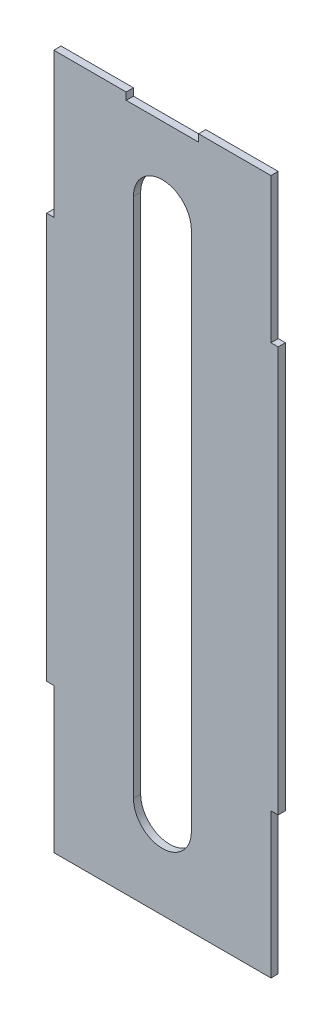
SolidWorks part; units mm, degrees
ref_plane "Front Plane" through (0, 0, 0) normal (0, 0, 1) x (1, 0, 0)
ref_plane "Top Plane" through (0, 0, 0) normal (0, 1, 0) x (1, 0, 0)
ref_plane "Right Plane" through (0, 0, 0) normal (1, 0, 0) x (0, 0, -1)
sketch "Sketch2" plane through (0, 0, 0) normal (0, 0, 1) x (1, 0, 0)
  line L1 (-803.1768, 65.3086) -> (-1019.0768, 65.3086)
  line L2 (-803.1768, 65.3086) -> (-803.1768, 674.9086)
  line L3 (-803.1768, 674.9086) -> (-1019.0768, 674.9086)
  line L4 (-1019.0768, 65.3086) -> (-1019.0768, 674.9086)
  line L5 (-803.1768, 65.3086) -> (-1019.0768, 674.9086) construction
  line L6 (-803.1768, 674.9086) -> (-1019.0768, 65.3086) construction
  dimension "D1" = 215.9
  dimension "D2" = 609.6
extrude "Boss-Extrude1" add sketch "Sketch2" along normal blind 6.35
sketch "Sketch3" plane through (0, 0, 6.35) normal (0, 0, 1) x (1, 0, 0)
  line L0 (-911.1268, 674.9086) -> (-911.1268, 65.3086) construction
  line L1 (-803.1768, 674.9086) -> (-1019.0768, 674.9086) construction
  line L2 (-1019.0768, 65.3086) -> (-803.1768, 65.3086) construction
  line L3 (-803.1768, 370.1086) -> (-1019.0768, 370.1086) construction
  line L4 (-803.1768, 65.3086) -> (-803.1768, 674.9086) construction
  line L5 (-1019.0768, 674.9086) -> (-1019.0768, 65.3086) construction
  line L6 (-911.1268, 141.5086) -> (-911.1268, 598.7086) construction
  line L7 (-936.5268, 141.5086) -> (-936.5268, 598.7086)
  line L8 (-885.7268, 141.5086) -> (-885.7268, 598.7086)
  arc A0 (-936.5268, 141.5086) -> (-885.7268, 141.5086) centre (-911.1268, 141.5086) ccw
  arc A1 (-885.7268, 598.7086) -> (-936.5268, 598.7086) centre (-911.1268, 598.7086) ccw
  point P14 (-911.1268, 370.1086)
extrude "Cut-Extrude1" cut sketch "Sketch3" against normal through all contours L8 A1 L7 A0
sketch "Sketch4" plane through (0, 0, 6.35) normal (0, 0, 1) x (1, 0, 0)
  line L0 (-815.8768, 674.9086) -> (-815.8768, 547.9086)
  line L1 (-803.1768, 674.9086) -> (-1019.0768, 674.9086) construction
  line L2 (-815.8768, 547.9086) -> (-803.1768, 547.9086)
  line L3 (-803.1768, 65.3086) -> (-803.1768, 674.9086) construction
extrude "Cut-Extrude2" cut sketch "Sketch4" against normal through all and the other way through all
sketch "Sketch5" plane through (0, 0, 6.35) normal (0, 0, 1) x (1, 0, 0)
  line L0 (-815.8768, 65.3086) -> (-815.8768, 192.3086)
  line L1 (-1019.0768, 65.3086) -> (-803.1768, 65.3086) construction
  line L2 (-815.8768, 192.3086) -> (-803.1768, 192.3086)
  line L3 (-803.1768, 65.3086) -> (-803.1768, 547.9086) construction
extrude "Cut-Extrude3" cut sketch "Sketch5" against normal through all and the other way through all flip side to cut
sketch "Sketch6" plane through (0, 0, 6.35) normal (0, 0, 1) x (1, 0, 0)
  line L0 (-1006.3768, 674.9086) -> (-1006.3768, 547.9086)
  line L1 (-815.8768, 674.9086) -> (-1019.0768, 674.9086) construction
  line L2 (-1006.3768, 547.9086) -> (-1019.0768, 547.9086)
  line L3 (-1019.0768, 674.9086) -> (-1019.0768, 65.3086) construction
extrude "Cut-Extrude6" cut sketch "Sketch6" against normal through all and the other way through all flip side to cut
ref_plane "Plane1" through (-1006.3768, 674.9086, 6.35) normal (-1, 0, 0) x (0, 0, 1)
sketch "Sketch9" plane through (0, 0, 6.35) normal (0, 0, 1) x (1, 0, 0)
  line L0 (-1006.3768, 65.3086) -> (-1006.3768, 192.3086)
  line L1 (-1019.0768, 65.3086) -> (-815.8768, 65.3086) construction
  line L2 (-1006.3768, 192.3086) -> (-1019.0768, 192.3086)
  line L3 (-1019.0768, 547.9086) -> (-1019.0768, 65.3086) construction
extrude "Cut-Extrude7" cut sketch "Sketch9" against normal through all and the other way through all
ref_plane "Plane2" through (-1006.3768, 65.3086, 6.35) normal (1, 0, 0) x (0, 0, -1)
sketch "Sketch13" plane through (0, 0, 0) normal (0, 0, -1) x (-1, 0, 0)
  line L2 (815.8768, 674.9086) -> (1006.3768, 674.9086) construction
  line L5 (879.3768, 668.5586) -> (879.3768, 674.9086)
  line L6 (942.8768, 668.5586) -> (942.8768, 674.9086)
  line L7 (942.8768, 668.5586) -> (879.3768, 668.5586)
ref_plane "Plane3" through (-803.1768, 192.3086, 0) normal (-1, 0, 0) x (0, 0, 1)
ref_plane "Plane10" through (-1019.0768, 192.3086, 6.35) normal (1, 0, 0) x (0, 0, -1)
sketch "Sketch16" plane through (0, 0, 6.35) normal (0, 0, 1) x (1, 0, 0)
  line L2 (-1012.7268, 192.3086) -> (-1012.7268, 547.9086)
  line L3 (-1019.0768, 192.3086) -> (-1006.3768, 192.3086) construction
  line L4 (-1019.0768, 547.9086) -> (-1006.3768, 547.9086) construction
extrude "Cut-Extrude11" cut sketch "Sketch16" against normal through all and the other way through all
sketch "Sketch17" plane through (0, 0, 6.35) normal (0, 0, 1) x (1, 0, 0)
  line L2 (-809.5268, 192.3086) -> (-809.5268, 547.9086)
  line L3 (-803.1768, 547.9086) -> (-815.8768, 547.9086) construction
extrude "Cut-Extrude13" cut sketch "Sketch17" against normal through all and the other way through all flip side to cut
extrude "Cut-Extrude14" cut sketch "Sketch13" against normal through all and the other way through all
